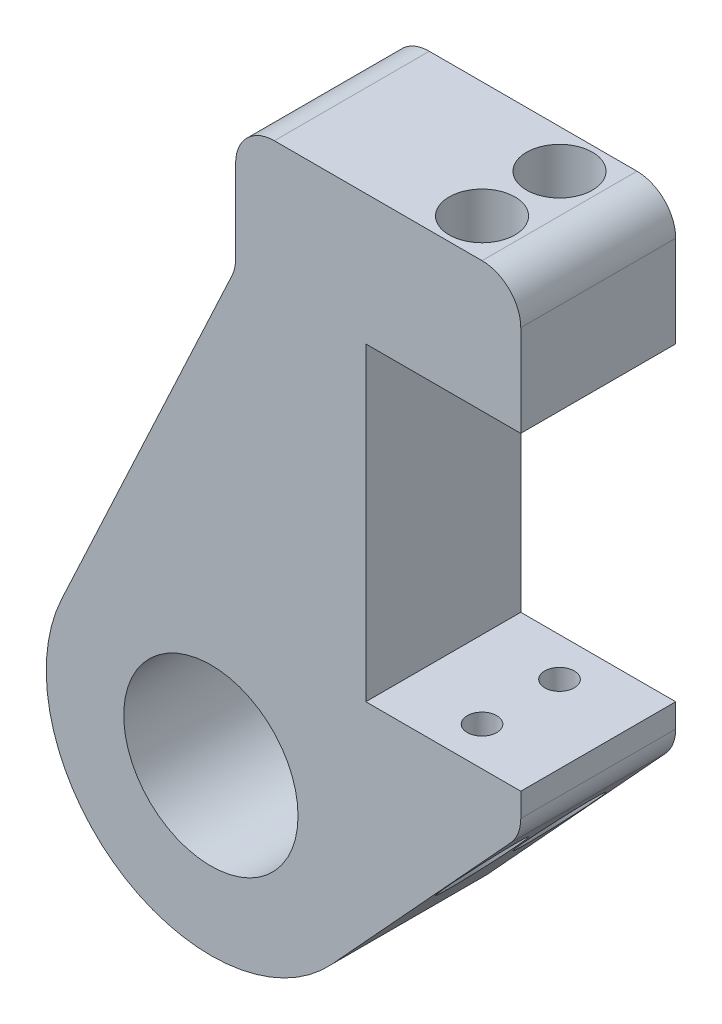
SolidWorks part; units mm, degrees
ref_plane "Front Plane" through (0, 0, 0) normal (0, 0, 1) x (1, 0, 0)
ref_plane "Top Plane" through (0, 0, 0) normal (0, 1, 0) x (1, 0, 0)
ref_plane "Right Plane" through (0, 0, 0) normal (1, 0, 0) x (0, 0, -1)
sketch "Sketch1" plane through (0, -13.0101, 793.75) normal (0, 0, 1) x (1, 0, 0)
  line L3 (-3.175, -125.9019) -> (-28.575, -125.9019)
  line L4 (-28.575, -75.1019) -> (-28.575, -125.9019)
  line L5 (-28.575, -75.1019) -> (-49.923, -75.1019) construction
  line L6 (-49.923, -75.1019) -> (-78.434, -136.2439)
  line L7 (-28.575, -75.1019) -> (-3.175, -75.1019)
  line L9 (-3.175, -75.1019) -> (-3.175, -53.7539)
  line L10 (-3.175, -53.7539) -> (-49.923, -53.7539)
  line L11 (-49.923, -75.1019) -> (-49.923, -53.7539)
  line L12 (-34.1032, -165.9096) -> (-3.175, -132.2519)
  line L13 (-3.175, -125.9019) -> (-3.175, -132.2519)
  circle A0 centre (-53.975, -147.6493) radius 14.2875
  arc A2 (-78.434, -136.2439) -> (-34.1032, -165.9096) centre (-53.975, -147.6493) ccw
  arc A4 (-39.9323, -145.0159) -> (-68.0177, -150.2826) centre (-53.975, -147.6493) ccw construction
  dimension "D1" = 12.7
  dimension "D5" = 28.575
  dimension "D2" = 65
  dimension "D3" = 21.348
  dimension "D4" = 6.35
extrude "Initial Plate" add sketch "Sketch1" along normal blind 25.4
sketch "Sketch3" plane through (0, -88.1119, 0) normal (0, -1, 0) x (1, 0, 0)
  line L0 (-15.875, 793.75) -> (-15.875, 800.1) construction
  line L1 (-28.575, 793.75) -> (-3.175, 793.75) construction
  circle A0 centre (-15.875, 800.1) radius 5.3975
  circle A1 centre (-15.875, 800.1) radius 2.413
  dimension "D2" = 4.826
  dimension "D3" = 10.795
  dimension "D1" = 6.35
extrude "Initial Bolt Hole" cut sketch "Sketch3" against normal through all and the other way through all contours A1
extrude "Initial Head Hole" cut sketch "Sketch3<3>" against normal through all from offset 12.7 offset against normal yes
sketch "Sketch3<3>" plane through (0, -88.1119, 0) normal (0, -1, 0) x (1, 0, 0) same geometry as "Sketch3"
extrude "Other Head Hole" cut sketch "Sketch3<4>" against normal offset from surface (27.3077 mm away) 12.7 from vertex up to face at (-15.875, -138.9119, 797.687) starting at point (-34.1032, -178.9197, 793.75)
sketch "Sketch3<4>" plane through (0, -88.1119, 0) normal (0, -1, 0) x (1, 0, 0) same geometry as "Sketch3"
pattern_linear "Mounting Pattern" count 2 spacing 12.7 along (0, 0, 1) of "Initial Head Hole", "Initial Bolt Hole", "Other Head Hole"
fillet "Fillet1" radius 6.35 4 edges at (-3.175, -66.764, 806.45) (-49.923, -88.1119, 806.45) (-49.923, -66.764, 806.45) (-3.175, -145.2619, 806.45)
